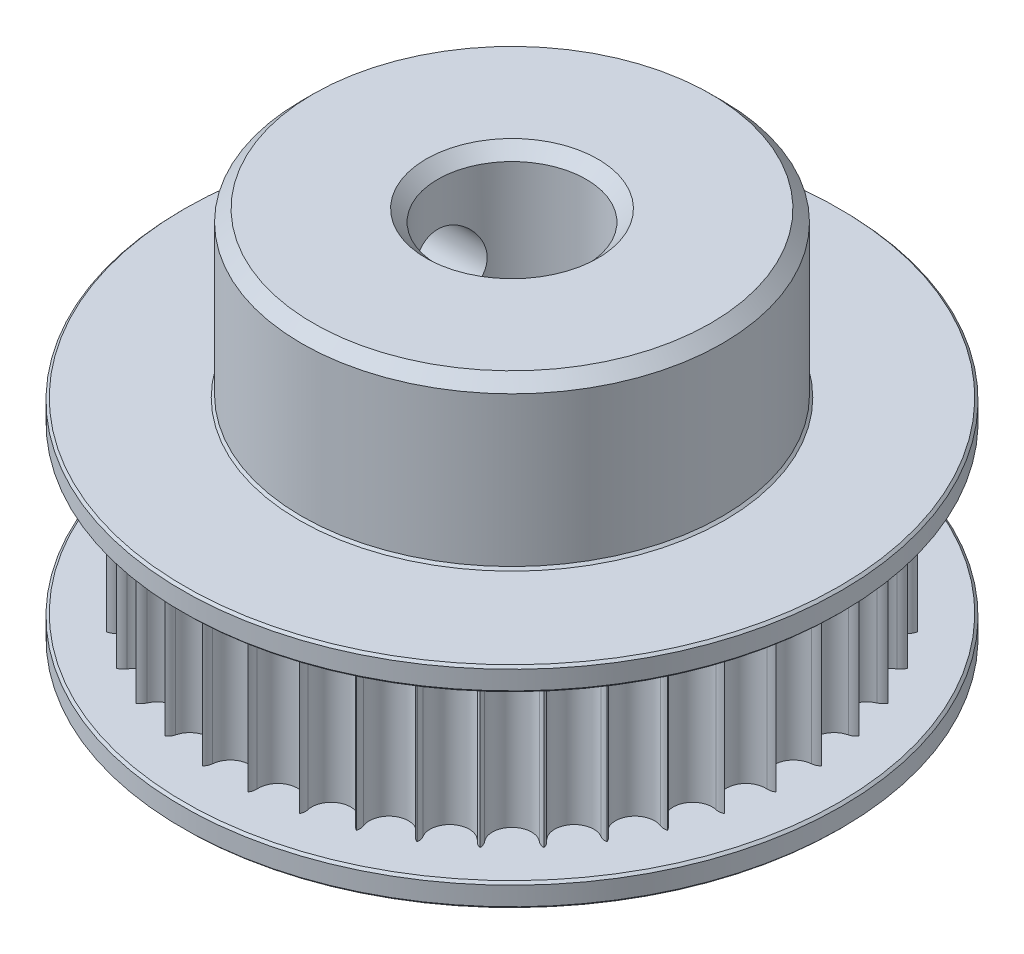
SolidWorks part; units mm, degrees
ref_plane "Front plan" through (0, 0, 0) normal (0, 0, 1) x (1, 0, 0)
ref_plane "Top plan" through (0, 0, 0) normal (0, 1, 0) x (1, 0, 0)
ref_plane "Right plan" through (0, 0, 0) normal (1, 0, 0) x (0, 0, -1)
sketch "Skica2" plane through (0, 0, 0) normal (0, 0, 1) x (1, 0, 0)
  line L0 (9, 8.5) -> (3.175, 8.5)
  line L1 (3.175, 8.5) -> (3.175, -8.5)
  line L2 (3.175, -8.5) -> (6.11, -8.5)
  line L3 (0, -8.5) -> (0, 8.5) construction
  line L4 (0, 8.5) -> (3.175, 8.5)
  line L5 (0, -8.5) -> (3.175, -8.5)
  line L6 (6.11, -8.5) -> (6.11, -7.5)
  line L7 (14.1, 0.5) -> (12.5, 0.5)
  line L8 (12.5, 0.5) -> (12.5, -6.5)
  line L9 (14.1, 0.5) -> (14.1, 1.5)
  line L12 (14.1, -7.5) -> (6.11, -7.5)
  line L13 (14.1, 1.5) -> (9, 1.5)
  line L14 (14.1, -7.5) -> (14.1, -6.5)
  line L15 (12.5, -6.5) -> (14.1, -6.5)
  line L16 (9, 1.5) -> (9, 8.5)
  point P6 (10.105, -7.5)
  point P7 (0, 0)
  dimension "D2" = 1
  dimension "D6" = 28.2
  dimension "D3" = 25
  dimension "D1" = 6.35
  dimension "D8" = 17
  dimension "D4" = 1
  dimension "D7" = 18
  dimension "D9" = 7
revolve "Revolute" add sketch "Skica2" angle 360 about L3 region at (7.354, -0.6189, 0)
sketch "Sketch2" plane through (0, 0.5, 0) normal (0, -1, 0) x (1, 0, 0)
  line L0 (0, 0) -> (0, 12.0464) construction
  line L1 (0, 0) -> (4.215, 11.7679) construction
  line L3 (0, 0) -> (-2.1557, 12.3127) construction
  circle A1 centre (0, 0) radius 11.2105 construction
  circle A2 centre (0, 0) radius 12 construction
  arc A3 (-0.8326, 11.9711) -> (0.8326, 11.9711) centre (0, 12.0464) ccw
  arc A7 (-1.386, 12.4229) -> (-2.1557, 12.3127) centre (0, 0) ccw
  arc A8 (0, 13.9436) -> (2.1557, 12.3127) centre (0.592, 12.486) cw
  circle A9 centre (0, 0) radius 12.5 construction
  arc A10 (1.386, 12.4229) -> (2.1557, 12.3127) centre (0, 0) cw
  arc A11 (1.386, 12.4229) -> (0.8326, 11.9711) centre (1.3305, 11.926) ccw
  arc A12 (0, 13.9436) -> (-2.1557, 12.3127) centre (-0.592, 12.486) ccw
  arc A13 (-1.386, 12.4229) -> (-0.8326, 11.9711) centre (-1.3305, 11.926) cw
  point P0 (0.8326, 11.926)
  dimension "D2" = 1
  dimension "D4" = 0.836
  dimension "D6" = 25
  dimension "D3" = 1.5733
  dimension "D1" = 0.5
extrude "Cut-Extrude3" cut sketch "Sketch2" along normal up to surface (7 mm away) up to face at (14.1, -6.5, 0)
pattern_circular "CirPattern1" count 40 over 360 about axis through (0, -8.5, 0) along (0, -1, 0) of "Cut-Extrude3"
sketch "Sketch3" plane through (0, 0, 0) normal (1, 0, 0) x (0, 0, -1)
  line L0 (0, 8.5) -> (0, 0.5) construction
  line L1 (3.175, 8.5) -> (-3.175, 8.5) construction
  circle A0 centre (0, 4.5) radius 1.65
  dimension "D1" = 3.3
extrude "Cut-Extrude2" cut sketch "Sketch3" against normal up to next
chamfer "Chamfer1" distance 1 angle 45 1 edges at (6.11, -7.5, 0)
chamfer "Chamfer2" distance 0.5 angle 45 2 edges at (9, 8.5, 0) (3.175, 8.5, 0)
chamfer "Chamfer3" distance 0.1 angle 45 5 edges at (14.1, -7.5, 0) (14.1, -6.5, 0) (14.1, 0.5, 0) (14.1, 1.5, 0) (9, 1.5, 0)
equation "\"`\"=2"
equation "\"D6@Sketch2\"= \"D3@Skica2\""
